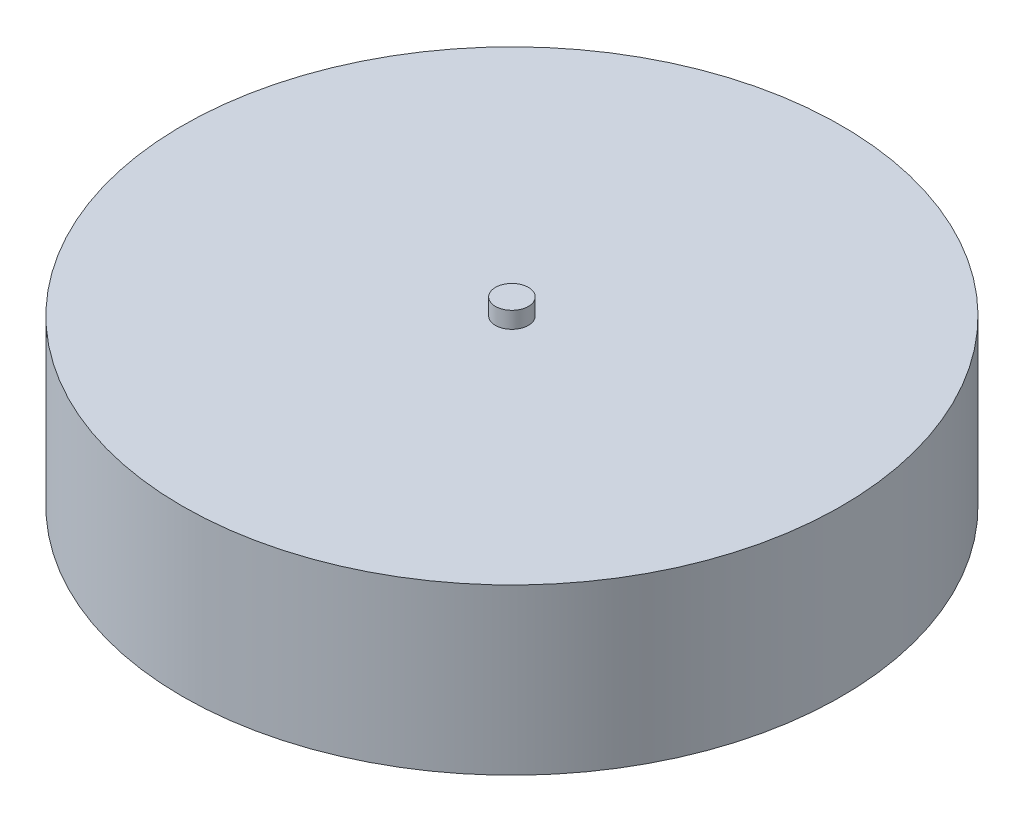
SolidWorks part; units mm, degrees
ref_plane "Front Plane" through (0, 0, 0) normal (0, 0, 1) x (1, 0, 0)
ref_plane "Top Plane" through (0, 0, 0) normal (0, 1, 0) x (1, 0, 0)
ref_plane "Right Plane" through (0, 0, 0) normal (1, 0, 0) x (0, 0, -1)
sketch "Sketch1" plane through (0, 0, 0) normal (0, 1, 0) x (1, 0, 0)
  circle A0 centre (0, 0) radius 200
  circle A1 centre (0, 0) radius 10
  dimension "D1" = 400
extrude "Boss-Extrude1" add sketch "Sketch1" along normal blind 100 contours A0
extrude "Boss-Extrude2" add sketch "Sketch1<3>" along normal blind 110 and the other way blind 10 separate body contours A1
sketch "Sketch1<3>" plane through (0, 0, 0) normal (0, 1, 0) x (1, 0, 0) same geometry as "Sketch1"
ref_plane "Plane1" through (0, 0, 0) normal (0, 0, 1) x (1, 0, 0)
sketch "Sketch2" plane through (0, 0, 0) normal (0, 0, 1) x (1, 0, 0)
  line L0 (0, 0) -> (0, -376.1833) construction
